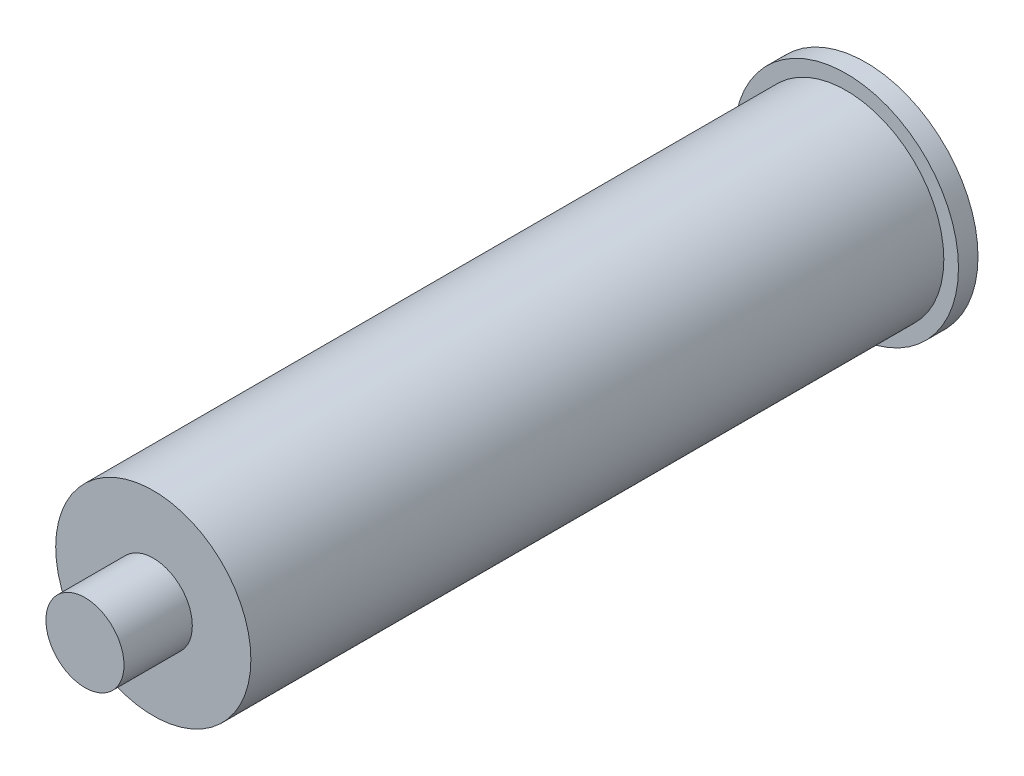
SolidWorks part; units mm, degrees
ref_plane "Front Plane" through (0, 0, 0) normal (0, 0, 1) x (1, 0, 0)
ref_plane "Top Plane" through (0, 0, 0) normal (0, 1, 0) x (1, 0, 0)
ref_plane "Right Plane" through (0, 0, 0) normal (1, 0, 0) x (0, 0, -1)
other "Configuration Table"
sketch "Sketch1" plane through (0, 0, 0) normal (0, 0, 1) x (1, 0, 0)
  circle A0 centre (0, 0) radius 10
  dimension "D1" = 20
extrude "Boss-Extrude1" add sketch "Sketch1" along normal blind 35.5 and the other way blind 35.5
sketch "Sketch2" plane through (0, 0, -35.5) normal (0, 0, -1) x (-1, 0, 0)
  line L1 (7.1014, 0) -> (3.5507, 6.15)
  line L2 (3.5507, 6.15) -> (-3.5507, 6.15)
  line L3 (-3.5507, 6.15) -> (-7.1014, 0)
  line L4 (-7.1014, 0) -> (-3.5507, -6.15)
  line L5 (-3.5507, -6.15) -> (3.5507, -6.15)
  line L6 (3.5507, -6.15) -> (7.1014, 0)
  circle A0 centre (0, 0) radius 6.15 construction
  dimension "D1" = 12.3
extrude "Cut-Extrude1" cut sketch "Sketch2" against normal blind 6
sketch "Sketch3" plane through (0, 0, 35.5) normal (0, 0, 1) x (1, 0, 0)
  circle A0 centre (0, 0) radius 4
  dimension "D1" = 8
extrude "Boss-Extrude2" add sketch "Sketch3" along normal blind 7
sketch "Sketch4" plane through (0, 0, -35.5) normal (0, 0, -1) x (-1, 0, 0)
  circle A0 centre (0, 0) radius 8.5
  circle A1 centre (0, 0) radius 11.5
  dimension "D1" = 17
  dimension "D2" = 23
extrude "Boss-Extrude3" add sketch "Sketch4" along normal blind 2
